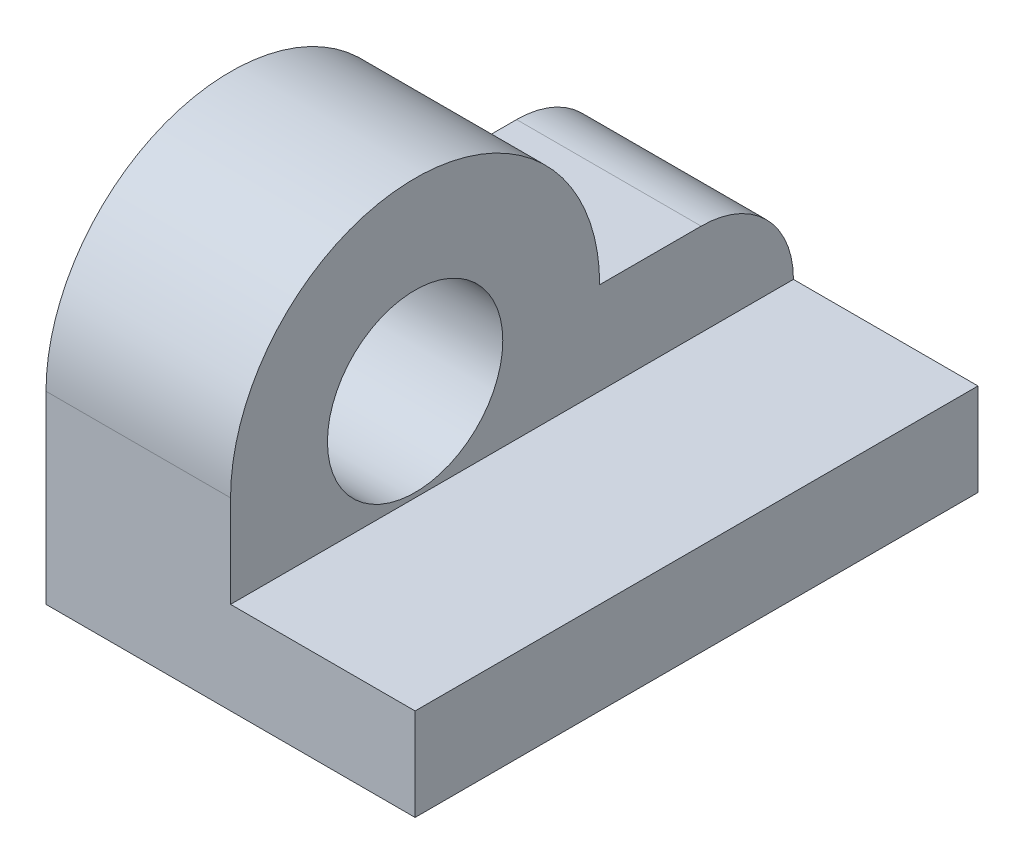
SolidWorks part; units mm, degrees
ref_plane "Front Plane" through (0, 0, 0) normal (0, 0, 1) x (1, 0, 0)
ref_plane "Top Plane" through (0, 0, 0) normal (0, 1, 0) x (1, 0, 0)
ref_plane "Right Plane" through (0, 0, 0) normal (1, 0, 0) x (0, 0, -1)
sketch "Sketch1" plane through (0, 0, 0) normal (0, 1, 0) x (1, 0, 0)
  line L1 (-20, 30.5) -> (20, 30.5)
  line L2 (-20, 30.5) -> (-20, -30.5)
  line L3 (-20, -30.5) -> (20, -30.5)
  line L4 (20, 30.5) -> (20, -30.5)
  line L5 (-20, 30.5) -> (20, -30.5) construction
  line L6 (-20, -30.5) -> (20, 30.5) construction
  point P0 (0, 0)
  dimension "D1" = 61
  dimension "D2" = 40
extrude "Boss-Extrude1" add sketch "Sketch1" along normal blind 40 contours L4 L3 L2 L1
sketch "Sketch2" plane through (0, 40, 0) normal (0, 1, 0) x (1, 0, 0)
  line L0 (0, 30.5) -> (0, -30.5)
  line L1 (-20, 30.5) -> (20, 30.5) construction
  line L2 (-20, -30.5) -> (20, -30.5) construction
  line L3 (-20, 30.5) -> (-20, -30.5) construction
  line L4 (0, 30.5) -> (20, 30.5)
  line L5 (20, 30.5) -> (20, -30.5)
  line L6 (20, -30.5) -> (0, -30.5)
  dimension "D1" = 20
extrude "Cut-Extrude1" cut sketch "Sketch2" against normal blind 30
sketch "Sketch3" plane through (0, 0, 0) normal (1, 0, 0) x (0, 0, -1)
  line L0 (30.5, 0) -> (-30.5, 0) construction
  line L1 (-30.5, 10) -> (-30.5, 40) construction
  line L2 (-26.9342, 20) -> (9.3157, 20) construction
  line L3 (-10.5, 37.2788) -> (-10.5, 3.4642) construction
  line L4 (-30.5, 20) -> (-20, 20)
  line L5 (-1, 20) -> (9.3157, 20)
  line L7 (9.5, 20) -> (20.4999, 20)
  line L8 (30.4998, 10.0473) -> (30.5, 10)
  line L10 (-30.5, 40) -> (30.5, 40)
  line L11 (30.5, 40) -> (30.5, 10)
  line L12 (30.5, 40) -> (-30.5, 40) construction
  line L13 (-30.5, 20) -> (-30.5, 40)
  circle A0 centre (-10.5, 20) radius 9.5
  arc A1 (9.5, 20) -> (-30.5, 20) centre (-10.5, 20) ccw
  arc A2 (20.4999, 20) -> (30.4998, 10.0473) centre (20.4999, 10) cw
  line M4 (30.5, 40) -> (-30.5, 40)
  line M5 (-30.5, 40) -> (-30.5, 10)
  line M7 (30.5, 10) -> (30.5, 40)
  dimension "D1" = 19
  dimension "D5" = 10
  dimension "D6" = 29.9527
  dimension "D2" = 20
  dimension "D3" = 20
extrude "Cut-Extrude3" cut sketch "Sketch3" against normal through all contours L7 A2 L8 A1 M7 M4 | A1 L10 M5 | A0 A1 region at (0, 20, 10.5) region at (0, 30.4028, -17.8999) region at (0, 35.5326, 26.0326)
